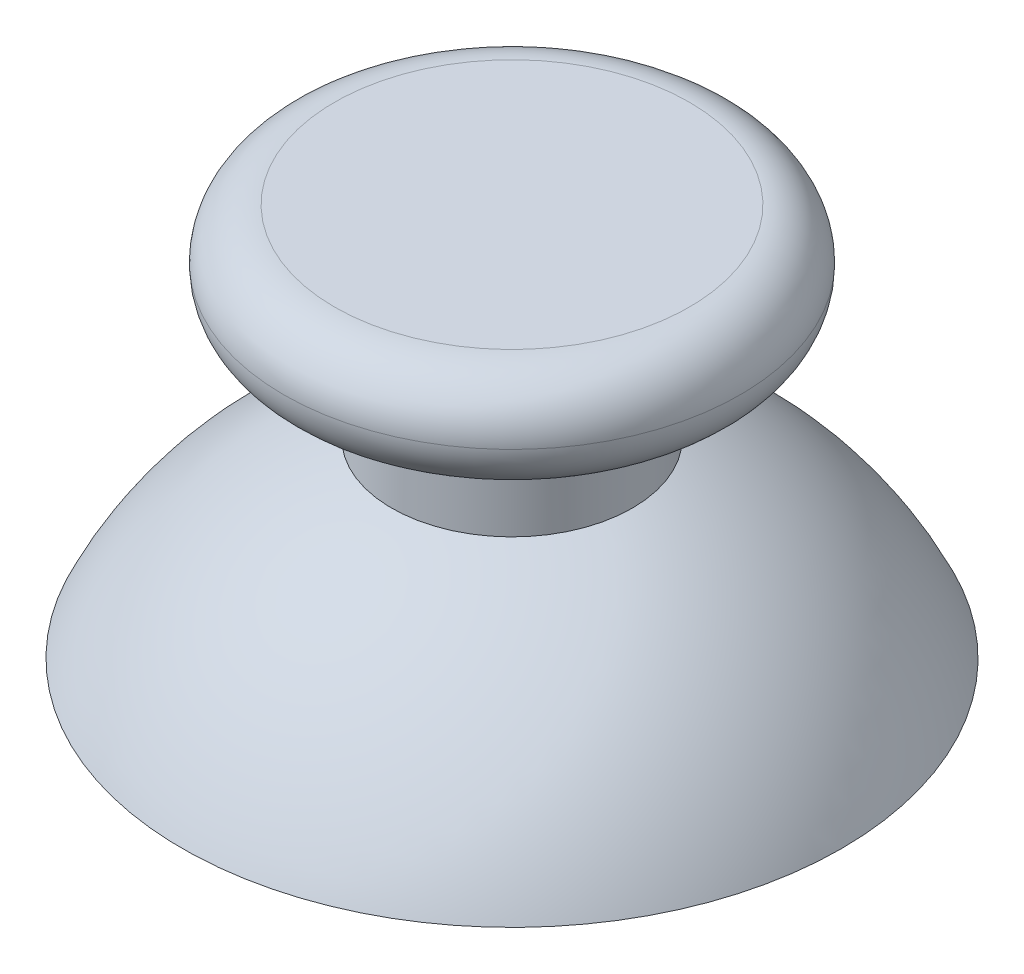
SolidWorks part; units mm, degrees
ref_plane "Front Plane" through (0, 0, 0) normal (0, 0, 1) x (1, 0, 0)
ref_plane "Top Plane" through (0, 0, 0) normal (0, 1, 0) x (1, 0, 0)
ref_plane "Right Plane" through (0, 0, 0) normal (1, 0, 0) x (0, 0, -1)
sketch "Sketch1" plane through (0, 0, 0) normal (0, 1, 0) x (1, 0, 0)
  circle A0 centre (0, 0) radius 4.75
  dimension "D1" = 9.5
extrude "Boss-Extrude1" add sketch "Sketch1" along normal blind 4
sketch "Sketch2" plane through (0, 4, 0) normal (0, 1, 0) x (1, 0, 0)
  circle A0 centre (0, 0) radius 9
  dimension "D1" = 18
extrude "Boss-Extrude2" add sketch "Sketch2" along normal blind 4
fillet "Fillet1" radius 2 2 edges at (0, 8, 9) (0, 4, 9)
sketch "Sketch5" plane through (0, 0, 0) normal (0, 0, 1) x (1, 0, 0)
  line L0 (0, -7.5) -> (0, 0.8178)
  line L1 (7, 8) -> (-7, 8) construction
  line L3 (13, -7.5) -> (0, -7.5)
  arc A0 (13, -7.5) -> (0, 0.8178) centre (0, -13.5) ccw
  point P5 (0, 0)
  dimension "D1" = 13
  dimension "D2" = 13.5
  dimension "D3" = 15.5
revolve "Revolve1" add sketch "Sketch5" angle 360 about L0
shell "Shell1" thickness 1 removed face at (0, -7.5, -13)
sketch "Sketch4" plane through (0, 0, 0) normal (0, -1, 0) x (-1, 0, 0)
  circle A0 centre (0, 0) radius 3.75
  dimension "D1" = 7.5
extrude "Boss-Extrude4" add sketch "Sketch4" against normal blind 2
